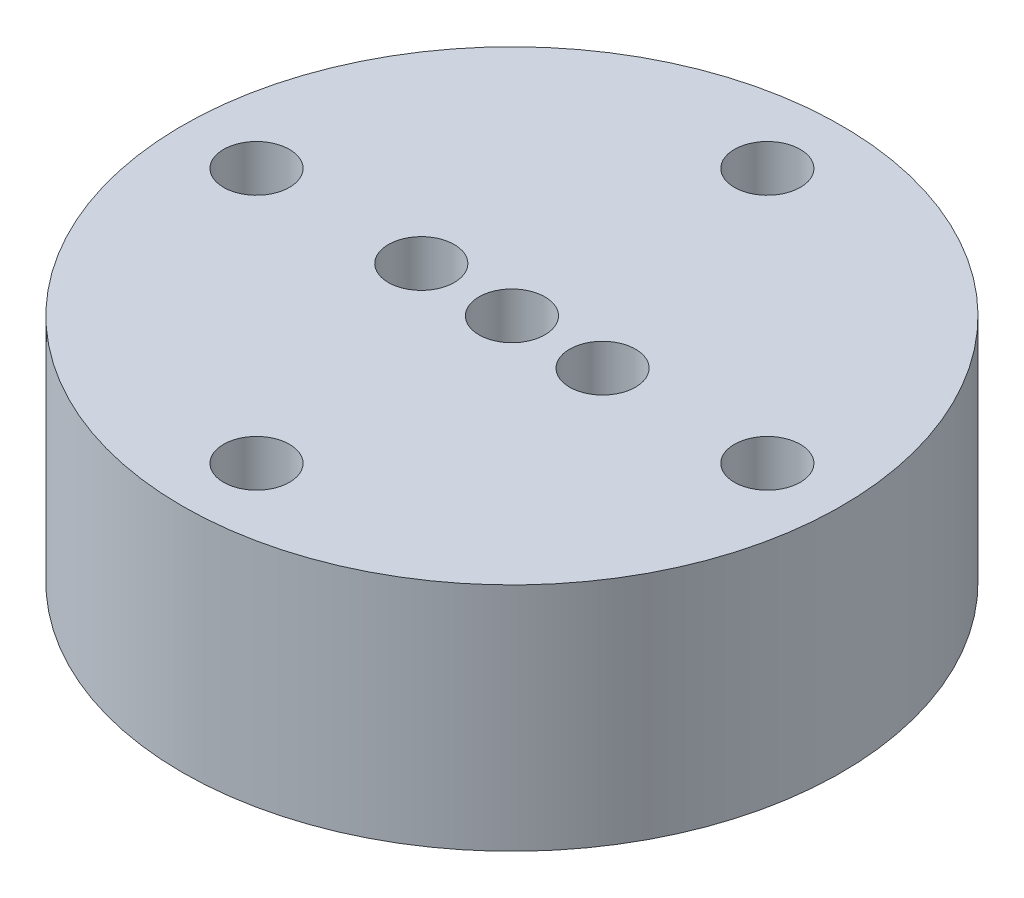
SolidWorks part; units mm, degrees
ref_plane "Front Plane" through (0, 0, 0) normal (0, 0, 1) x (1, 0, 0)
ref_plane "Top Plane" through (0, 0, 0) normal (0, 1, 0) x (1, 0, 0)
ref_plane "Right Plane" through (0, 0, 0) normal (1, 0, 0) x (0, 0, -1)
sketch "Sketch1" plane through (0, 0, 0) normal (0, 1, 0) x (1, 0, 0)
  circle A0 centre (0, 0) radius 15.5 construction
  circle A1 centre (0, 15.5) radius 2
  circle A2 centre (15.5, 0) radius 2
  circle A3 centre (0, -15.5) radius 2
  circle A4 centre (-15.5, 0) radius 2
  circle A5 centre (0, 0) radius 20
  circle A6 centre (0, 0) radius 4 construction
  point P14 (0, 0)
  dimension "D1" = 31
  dimension "D2" = 4
  dimension "D4" = 40
  dimension "D5" = 8
  dimension "D3" = 4
extrude "Boss-Extrude1" add sketch "Sketch1" along normal blind 14
sketch "Sketch2" plane through (0, 14, 0) normal (0, 1, 0) x (1, 0, 0)
  circle A0 centre (0, 0) radius 5.5 construction
  circle A1 centre (0, 0) radius 2
  circle A2 centre (5.5, 0) radius 2
  circle A3 centre (-5.5, 0) radius 2
  dimension "D1" = 11
  dimension "D2" = 4
  dimension "D3" = 4
  dimension "D4" = 4
extrude "Cut-Extrude1" cut sketch "Sketch2" against normal through all
